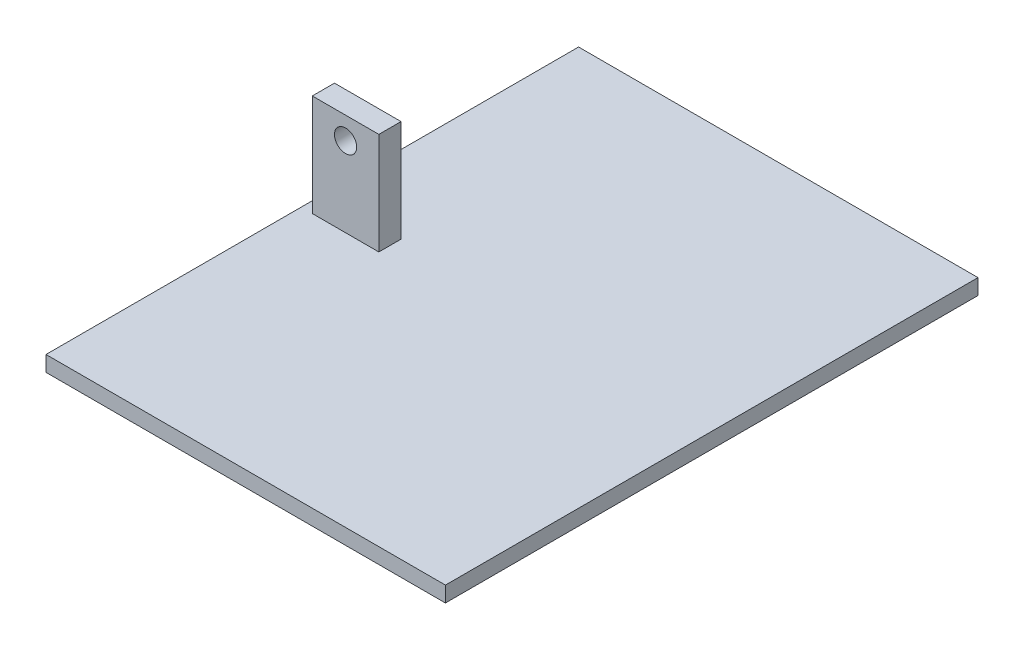
SolidWorks part; units mm, degrees
ref_plane "Front Plane" through (0, 0, 0) normal (0, 0, 1) x (1, 0, 0)
ref_plane "Top Plane" through (0, 0, 0) normal (0, 1, 0) x (1, 0, 0)
ref_plane "Right Plane" through (0, 0, 0) normal (1, 0, 0) x (0, 0, -1)
sketch "Sketch2" plane through (0, 0, 0) normal (0, 1, 0) x (1, 0, 0)
  line L0 (-228.6, 0) -> (-177.8, 0) construction
  line L1 (-228.6, 304.8) -> (228.6, 304.8)
  line L2 (-228.6, 304.8) -> (-228.6, -304.8)
  line L3 (-228.6, -304.8) -> (228.6, -304.8)
  line L4 (228.6, 304.8) -> (228.6, -304.8)
  line L5 (-228.6, 304.8) -> (228.6, -304.8) construction
  line L6 (-228.6, -304.8) -> (228.6, 304.8) construction
  line L8 (-215.9, 12.7) -> (-139.7, 12.7)
  line L9 (-215.9, 12.7) -> (-215.9, -12.7)
  line L10 (-215.9, -12.7) -> (-139.7, -12.7)
  line L11 (-139.7, 12.7) -> (-139.7, -12.7)
  line L12 (-215.9, 12.7) -> (-139.7, -12.7) construction
  line L13 (-215.9, -12.7) -> (-139.7, 12.7) construction
  point P0 (0, 0)
  dimension "D1" = 609.6
  dimension "D2" = 457.2
  dimension "D3" = 25.4
  dimension "D4" = 76.2
  dimension "D5" = 177.8
extrude "Boss-Extrude1" add sketch "Sketch2" against normal blind 17.78
sketch "Sketch3" plane through (0, 0, 0) normal (0, 1, 0) x (1, 0, 0)
  line L0 (-215.9, 12.7) -> (-215.9, -12.7) construction
  line L1 (-139.7, 12.7) -> (-215.9, 12.7) construction
  line L2 (-139.7, -12.7) -> (-139.7, 12.7) construction
  line L3 (-215.9, -12.7) -> (-139.7, -12.7) construction
  line L4 (-215.9, 12.7) -> (-215.9, -12.7)
  line L5 (-139.7, 12.7) -> (-215.9, 12.7)
  line L6 (-139.7, -12.7) -> (-139.7, 12.7)
  line L7 (-215.9, -12.7) -> (-139.7, -12.7)
extrude "Boss-Extrude2" add sketch "Sketch3" along normal blind 116.586 separate body
extrude "Boss-Extrude3" add sketch "Sketch3<2>" against normal blind 17.78
sketch "Sketch3<2>" plane through (0, 0, 0) normal (0, 1, 0) x (1, 0, 0) same geometry as "Sketch3"
sketch "Sketch4" plane through (0, 0, 0) normal (0, 0, 1) x (1, 0, 0)
  line L0 (-177.8, 116.586) -> (-177.8, 0) construction
  line L1 (-215.9, 116.586) -> (-139.7, 116.586) construction
  line L2 (-215.9, 0) -> (-139.7, 0) construction
  circle A0 centre (-177.8, 91.186) radius 12.7
  point P9 (-177.8, 58.293)
  dimension "D1" = 25.4
  dimension "D2" = 91.186
sketch "Sketch5" plane through (0, 0, 0) normal (0, 1, 0) x (1, 0, 0)
  line L0 (-228.6, 304.8) -> (-228.6, -304.8) construction
  line L1 (-196.85, -298.45) -> (-158.75, -298.45)
  line L2 (-196.85, -298.45) -> (-196.85, -260.35)
  line L3 (-196.85, -260.35) -> (-158.75, -260.35)
  line L4 (-158.75, -298.45) -> (-158.75, -260.35)
  line L5 (-196.85, -298.45) -> (-158.75, -260.35) construction
  line L6 (-196.85, -260.35) -> (-158.75, -298.45) construction
  line L7 (-196.85, 260.35) -> (-158.75, 260.35)
  line L8 (-196.85, 260.35) -> (-196.85, 298.45)
  line L9 (-196.85, 298.45) -> (-158.75, 298.45)
  line L10 (-158.75, 260.35) -> (-158.75, 298.45)
  line L11 (-196.85, 260.35) -> (-158.75, 298.45) construction
  line L12 (-196.85, 298.45) -> (-158.75, 260.35) construction
  line L13 (-228.6, -304.8) -> (228.6, -304.8) construction
  line L14 (-228.6, 304.8) -> (228.6, 304.8) construction
  line L15 (210.82, -304.8) -> (210.82, 304.8) construction
  line L16 (228.6, 304.8) -> (228.6, -304.8) construction
  point P0 (-177.8, -279.4)
  point P5 (-177.8, 279.4)
  dimension "D1" = 38.1
  dimension "D2" = 38.1
  dimension "D3" = 50.8
  dimension "D4" = 25.4
  dimension "D5" = 50.8
  dimension "D6" = 25.4
  dimension "D7" = 17.78
extrude "Cut-Extrude1" cut sketch "Sketch4" against normal blind 254 and the other way blind 254
